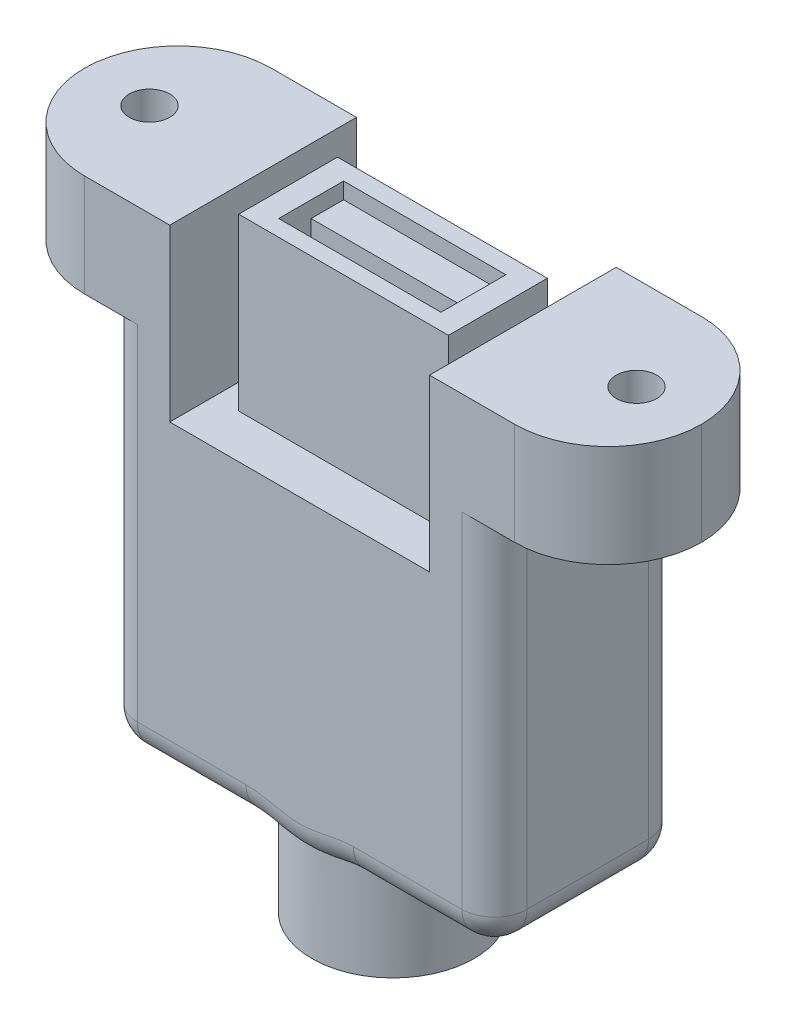
SolidWorks part; units mm, degrees
ref_plane "前视基准面" through (0, 0, 0) normal (0, 0, 1) x (1, 0, 0)
ref_plane "上视基准面" through (0, 0, 0) normal (0, 1, 0) x (1, 0, 0)
ref_plane "右视基准面" through (0, 0, 0) normal (1, 0, 0) x (0, 0, -1)
sketch "草图1" plane through (0, 0, 0) normal (0, 1, 0) x (1, 0, 0)
  line L1 (19, -5.75) -> (-19, -5.75)
  line L2 (19, -5.75) -> (19, 5.75)
  line L3 (19, 5.75) -> (-19, 5.75)
  line L4 (-19, -5.75) -> (-19, 5.75)
  line L5 (19, -5.75) -> (-19, 5.75) construction
  line L6 (19, 5.75) -> (-19, -5.75) construction
  point P0 (0, 0)
  dimension "D1" = 38
  dimension "D2" = 11.5
extrude "凸台-拉伸1" add sketch "草图1" along normal blind 6.3
fillet "圆角1" radius 5.76 4 edges at (-19, 3.15, 5.75) (-19, 3.15, -5.75) (19, 3.15, -5.75) (19, 3.15, 5.75)
sketch "草图2" plane through (0, 0, 0) normal (0, -1, 0) x (1, 0, 0)
  line L0 (-13.24, 5.75) -> (13.24, 5.75) construction
  line L1 (12, -5.75) -> (-12, -5.75)
  line L2 (12, -5.75) -> (12, 5.75)
  line L3 (12, 5.75) -> (-12, 5.75)
  line L4 (-12, -5.75) -> (-12, 5.75)
  line L5 (12, -5.75) -> (-12, 5.75) construction
  line L6 (12, 5.75) -> (-12, -5.75) construction
  point P0 (0, 0)
  dimension "D1" = 24
extrude "凸台-拉伸2" add sketch "草图2" along normal blind 23.2
sketch "草图3" plane through (0, -23.2, 0) normal (0, -1, 0) x (1, 0, 0)
  circle A0 centre (0, 0) radius 5
  dimension "D1" = 10
extrude "凸台-拉伸3" add sketch "草图3" along normal blind 6
sketch "草图4" plane through (0, 0, -5.75) normal (0, 0, -1) x (-1, 0, 0)
  line L0 (-13.24, 6.3) -> (13.24, 6.3) construction
  line L1 (-8, 6.3) -> (8, 6.3)
  line L2 (-8, 6.3) -> (-8, -4.2)
  line L3 (-8, -4.2) -> (8, -4.2)
  line L4 (8, 6.3) -> (8, -4.2)
  line L5 (0, 0) -> (0, 5.7149) construction
  dimension "D1" = 10.5
  dimension "D2" = 16
extrude "切除-拉伸1" cut sketch "草图4" against normal through all
sketch "草图5" plane through (0, -4.2, 0) normal (0, 1, 0) x (1, 0, 0)
  line L1 (6.4614, -3.0443) -> (-6.4614, -3.0443)
  line L2 (6.4614, -3.0443) -> (6.4614, 3.0443)
  line L3 (6.4614, 3.0443) -> (-6.4614, 3.0443)
  line L4 (-6.4614, -3.0443) -> (-6.4614, 3.0443)
  line L5 (6.4614, -3.0443) -> (-6.4614, 3.0443) construction
  line L6 (6.4614, 3.0443) -> (-6.4614, -3.0443) construction
  point P0 (0, 0)
extrude "凸台-拉伸4" add sketch "草图5" along normal up to surface (10.5 mm away) up to face at (-12.7718, 6.3, 0)
hole_wizard "M3 螺纹孔1" positions "草图6" profile "草图7" tap size "M3" standard "GB" end condition up to next
sketch "草图6" plane through (0, 6.3, 0) normal (0, 1, 0) x (1, 0, 0)
  line L0 (0, 0) -> (0, -3.0443) construction
  line L1 (-6.4614, -3.0443) -> (6.4614, -3.0443) construction
  point P0 (15, 0)
  point P2 (-15, 0)
  dimension "D1" = 30
sketch "草图7" plane through (15, 6.3, 0) normal (1, 0, 0) x (0, 0, 1)
  line L0 (0, 0) -> (0, 6.3)
  line L1 (0, 6.3) -> (1.25, 6.3)
  line L2 (1.25, 6.3) -> (1.25, 0)
  line L5 (1.25, 0) -> (0, 0)
  line L11 (0, -6.35) -> (0, 107.95) construction
  dimension "通孔螺纹孔钻头直径" = 2.5
  dimension "通孔螺纹孔钻头深度" = 6.3
cosmetic thread "孔螺蚊线1" parameters "D2"=3
cosmetic thread "孔螺蚊线2" parameters "D2"=3
fillet "圆角2" radius 2 8 edges at (12, -23.2, 0) (0, -23.2, 5.75) (-12, -23.2, 0) (0, -23.2, -5.75) (-12, -11.6, -5.75) (12, -11.6, -5.75) (-12, -11.6, 5.75) (12, -11.6, 5.75)
sketch "草图8" plane through (0, 6.3, 0) normal (0, 1, 0) x (1, 0, 0)
  line L0 (-6.4614, -3.0443) -> (6.4614, -3.0443) construction
  line L1 (5, -2.0443) -> (-5, -2.0443)
  line L2 (5, -2.0443) -> (5, -0.0443)
  line L3 (5, -0.0443) -> (-5, -0.0443)
  line L4 (-5, -2.0443) -> (-5, -0.0443)
  line L5 (5, -2.0443) -> (-5, -0.0443) construction
  line L6 (5, -0.0443) -> (-5, -2.0443) construction
  point P0 (0, -1.0443)
  dimension "D1" = 10
  dimension "D2" = 1
  dimension "D3" = 2
extrude "切除-拉伸2" cut sketch "草图8" against normal blind 6
sketch "草图9" plane through (0, 6.3, 0) normal (0, 1, 0) x (1, 0, 0)
  line L0 (5, -2.0443) -> (5, -0.0443) construction
  line L1 (-5, -0.0443) -> (5, -0.0443)
  line L2 (-5, -0.0443) -> (-5, 1.9557)
  line L3 (-5, 1.9557) -> (5, 1.9557)
  line L4 (5, -0.0443) -> (5, 1.9557)
  dimension "D1" = 2
extrude "切除-拉伸3" cut sketch "草图9" against normal blind 1
